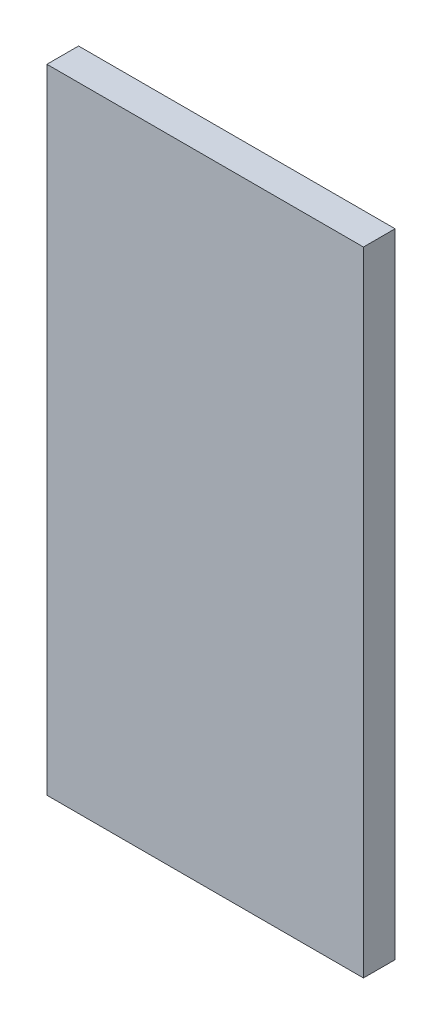
SolidWorks part; units mm, degrees
material "6061-T6 (SS)"
ref_plane "Alzado" through (0, 0, 0) normal (0, 0, 1) x (1, 0, 0)
ref_plane "Planta" through (0, 0, 0) normal (0, 1, 0) x (1, 0, 0)
ref_plane "Vista lateral" through (0, 0, 0) normal (1, 0, 0) x (0, 0, -1)
sketch "Sketch1" plane through (0, 0, 0) normal (0, 0, 1) x (1, 0, 0)
  line L1 (-20, 40) -> (20, 40)
  line L2 (-20, 40) -> (-20, -40)
  line L3 (-20, -40) -> (20, -40)
  line L4 (20, 40) -> (20, -40)
  line L5 (-20, 40) -> (20, -40) construction
  line L6 (-20, -40) -> (20, 40) construction
  point P0 (0, 0)
  dimension "D1" = 40
  dimension "D2" = 80
extrude "Boss-Extrude1" add sketch "Sketch1" along normal blind 4
sketch "Sketch2" plane through (0, 0, 4) normal (0, 0, 1) x (1, 0, 0)
  line L5 (20, 1.25) -> (0, 1.25)
  line L12 (20, -40) -> (20, 40) construction
  line L13 (0, 1.25) -> (0, -1.25)
  line L14 (0, -1.25) -> (20, -1.25)
  line L15 (20, -1.25) -> (20, 1.25)
  point P8 (0, 0)
  dimension "D1" = 2.5
extrude "Cut-Extrude1" [suppressed] cut sketch "Sketch2" against normal blind 10
fillet "Fillet1" [suppressed] radius 2
